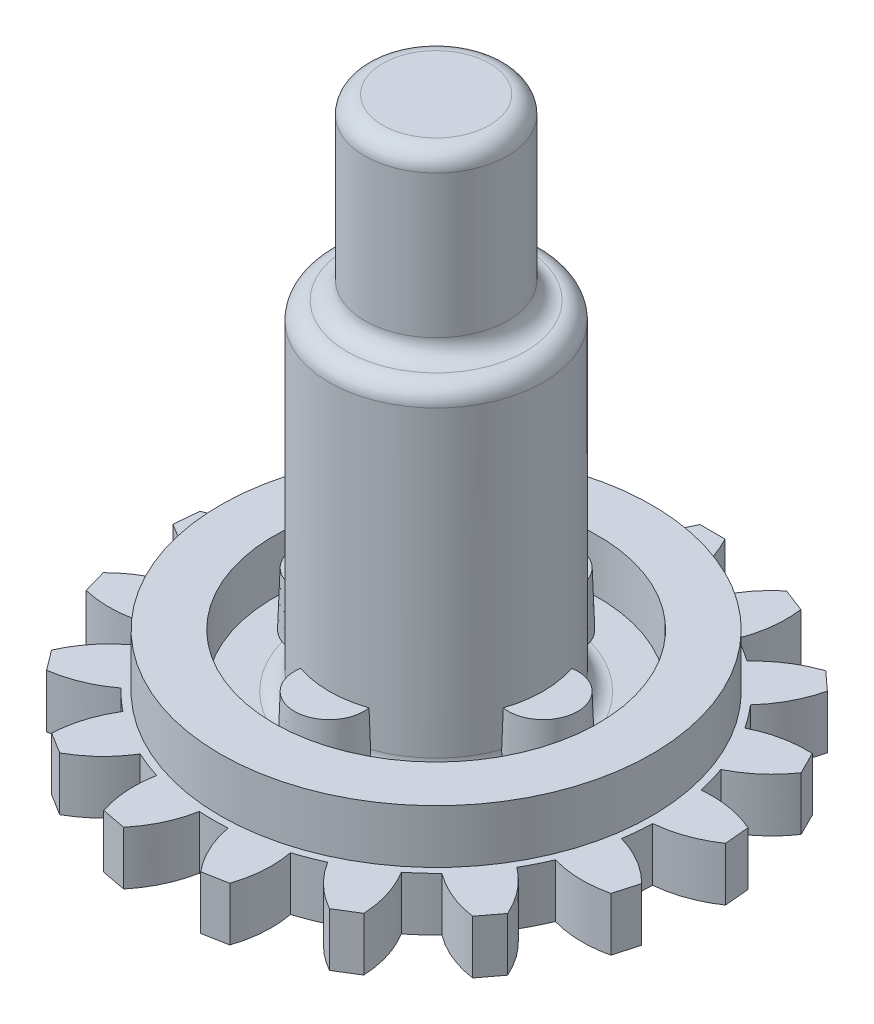
SolidWorks part; units mm, degrees
ref_plane "Front Plane" through (0, 0, 0) normal (0, 0, 1) x (1, 0, 0)
ref_plane "Top Plane" through (0, 0, 0) normal (0, 1, 0) x (1, 0, 0)
ref_plane "Right Plane" through (0, 0, 0) normal (1, 0, 0) x (0, 0, -1)
sketch "Sketch2" plane through (0, 0, 0) normal (0, 1, 0) x (1, 0, 0)
  line L0 (0, 12.5) -> (0, 15.5) construction
  line L1 (0, 14) -> (1.3, 14) construction
  line L2 (-0.7, 15.5) -> (0.7, 15.5)
  line L3 (4.9465, 14.7062) -> (6.252, 14.2005)
  line L4 (9.925, 11.9262) -> (10.9596, 10.9831)
  line L5 (13.563, 7.5356) -> (14.187, 6.2823)
  line L6 (15.3693, 2.1272) -> (15.4985, 0.7331)
  line L7 (15.0999, -3.5685) -> (14.7167, -4.9151)
  line L8 (12.7911, -8.7822) -> (11.9474, -9.8994)
  line L9 (8.7549, -12.8099) -> (7.5645, -13.5469)
  line L10 (3.5362, -15.1075) -> (2.16, -15.3647)
  line L11 (-2.16, -15.3647) -> (-3.5362, -15.1075)
  line L12 (-7.5645, -13.5469) -> (-8.7549, -12.8099)
  line L13 (-11.9474, -9.8994) -> (-12.7911, -8.7822)
  line L14 (-14.7167, -4.9151) -> (-15.0999, -3.5685)
  line L15 (-15.4985, 0.7331) -> (-15.3693, 2.1272)
  line L16 (-14.187, 6.2823) -> (-13.563, 7.5356)
  line L17 (-10.9596, 10.9831) -> (-9.925, 11.9262)
  line L18 (-6.252, 14.2005) -> (-4.9465, 14.7062)
  circle A0 centre (0, 0) radius 8.9
  circle A1 centre (0, 0) radius 12.5 construction
  arc A2 (1.5, 12.4097) -> (3.0842, 12.1135) centre (0, 0) cw
  arc A3 (5.8816, 11.0298) -> (7.2518, 10.1814) centre (0, 0) cw
  arc A4 (9.4689, 8.1603) -> (10.4401, 6.8742) centre (0, 0) cw
  arc A5 (11.7773, 4.1887) -> (12.2183, 2.6386) centre (0, 0) cw
  arc A6 (12.4951, -0.3486) -> (12.3464, -1.9533) centre (0, 0) cw
  arc A7 (11.5254, -4.8388) -> (10.8071, -6.2815) centre (0, 0) cw
  arc A8 (8.9992, -8.6755) -> (7.8082, -9.7613) centre (0, 0) cw
  arc A9 (5.2575, -11.3406) -> (3.7547, -11.9228) centre (0, 0) cw
  arc A10 (0.8058, -12.474) -> (-0.8058, -12.474) centre (0, 0) cw
  arc A11 (-3.7547, -11.9228) -> (-5.2575, -11.3406) centre (0, 0) cw
  arc A12 (-7.8082, -9.7613) -> (-8.9992, -8.6755) centre (0, 0) cw
  arc A13 (-10.8071, -6.2815) -> (-11.5254, -4.8388) centre (0, 0) cw
  arc A14 (-12.3464, -1.9533) -> (-12.4951, -0.3486) centre (0, 0) cw
  arc A15 (-12.2183, 2.6386) -> (-11.7773, 4.1887) centre (0, 0) cw
  arc A16 (-10.4401, 6.8742) -> (-9.4689, 8.1603) centre (0, 0) cw
  arc A17 (-7.2518, 10.1814) -> (-5.8816, 11.0298) centre (0, 0) cw
  arc A18 (-3.0842, 12.1135) -> (-1.5, 12.4097) centre (0, 0) cw
  spline S0 degree 2 poles (0.7, 15.5) (1.4969, 14.0574) (1.5, 12.4097) knots 0 0 0 1 1 1
  spline S1 degree 2 poles (-0.7, 15.5) (-1.4969, 14.0574) (-1.5, 12.4097) knots 0 0 0 1 1 1
  spline S2 degree 2 poles (6.252, 14.2005) (6.4739, 12.5674) (5.8816, 11.0298) knots 0 0 0 1 1 1
  spline S3 degree 2 poles (4.9465, 14.7062) (3.6823, 13.6488) (3.0842, 12.1135) knots 0 0 0 1 1 1
  spline S4 degree 2 poles (10.9596, 10.9831) (10.5766, 9.3801) (9.4689, 8.1603) knots 0 0 0 1 1 1
  spline S5 degree 2 poles (9.925, 11.9262) (8.3642, 11.3969) (7.2518, 10.1814) knots 0 0 0 1 1 1
  spline S6 degree 2 poles (14.187, 6.2823) (13.2508, 4.926) (11.7773, 4.1887) knots 0 0 0 1 1 1
  spline S7 degree 2 poles (13.563, 7.5356) (11.9164, 7.6058) (10.4401, 6.8742) knots 0 0 0 1 1 1
  spline S8 degree 2 poles (15.4985, 0.7331) (14.1355, -0.1934) (12.4951, -0.3486) knots 0 0 0 1 1 1
  spline S9 degree 2 poles (15.3693, 2.1272) (13.8593, 2.7875) (12.2183, 2.6386) knots 0 0 0 1 1 1
  spline S10 degree 2 poles (14.7167, -4.9151) (13.1111, -5.2867) (11.5254, -4.8388) knots 0 0 0 1 1 1
  spline S11 degree 2 poles (15.0999, -3.5685) (13.9304, -2.4073) (12.3464, -1.9533) knots 0 0 0 1 1 1
  spline S12 degree 2 poles (11.9474, -9.8994) (10.316, -9.666) (8.9992, -8.6755) knots 0 0 0 1 1 1
  spline S13 degree 2 poles (12.7911, -8.7822) (12.1201, -7.2769) (10.8071, -6.2815) knots 0 0 0 1 1 1
  spline S14 degree 2 poles (7.5645, -13.5469) (6.1276, -12.7398) (5.2575, -11.3406) knots 0 0 0 1 1 1
  spline S15 degree 2 poles (8.7549, -12.8099) (8.6729, -11.1638) (7.8082, -9.7613) knots 0 0 0 1 1 1
  spline S16 degree 2 poles (2.16, -15.3647) (1.1117, -14.093) (0.8058, -12.474) knots 0 0 0 1 1 1
  spline S17 degree 2 poles (3.5362, -15.1075) (4.0544, -13.543) (3.7547, -11.9228) knots 0 0 0 1 1 1
  spline S18 degree 2 poles (-3.5362, -15.1075) (-4.0544, -13.543) (-3.7547, -11.9228) knots 0 0 0 1 1 1
  spline S19 degree 2 poles (-2.16, -15.3647) (-1.1117, -14.093) (-0.8058, -12.474) knots 0 0 0 1 1 1
  spline S20 degree 2 poles (-8.7549, -12.8099) (-8.6729, -11.1638) (-7.8082, -9.7613) knots 0 0 0 1 1 1
  spline S21 degree 2 poles (-7.5645, -13.5469) (-6.1276, -12.7398) (-5.2575, -11.3406) knots 0 0 0 1 1 1
  spline S22 degree 2 poles (-12.7911, -8.7822) (-12.1201, -7.2769) (-10.8071, -6.2815) knots 0 0 0 1 1 1
  spline S23 degree 2 poles (-11.9474, -9.8994) (-10.316, -9.666) (-8.9992, -8.6755) knots 0 0 0 1 1 1
  spline S24 degree 2 poles (-15.0999, -3.5685) (-13.9304, -2.4073) (-12.3464, -1.9533) knots 0 0 0 1 1 1
  spline S25 degree 2 poles (-14.7167, -4.9151) (-13.1111, -5.2867) (-11.5254, -4.8388) knots 0 0 0 1 1 1
  spline S26 degree 2 poles (-15.3693, 2.1272) (-13.8593, 2.7875) (-12.2183, 2.6386) knots 0 0 0 1 1 1
  spline S27 degree 2 poles (-15.4985, 0.7331) (-14.1355, -0.1934) (-12.4951, -0.3486) knots 0 0 0 1 1 1
  spline S28 degree 2 poles (-13.563, 7.5356) (-11.9164, 7.6058) (-10.4401, 6.8742) knots 0 0 0 1 1 1
  spline S29 degree 2 poles (-14.187, 6.2823) (-13.2508, 4.926) (-11.7773, 4.1887) knots 0 0 0 1 1 1
  spline S30 degree 2 poles (-9.925, 11.9262) (-8.3642, 11.3969) (-7.2518, 10.1814) knots 0 0 0 1 1 1
  spline S31 degree 2 poles (-10.9596, 10.9831) (-10.5766, 9.3801) (-9.4689, 8.1603) knots 0 0 0 1 1 1
  spline S32 degree 2 poles (-4.9465, 14.7062) (-3.6823, 13.6488) (-3.0842, 12.1135) knots 0 0 0 1 1 1
  spline S33 degree 2 poles (-6.252, 14.2005) (-6.4739, 12.5674) (-5.8816, 11.0298) knots 0 0 0 1 1 1
  point P113 (0, 0)
  point P146 (0, 0)
  dimension "D1" = 17.8
  dimension "D5" = 25
  dimension "D2" = 0.7
  dimension "D3" = 1.5
  dimension "D4" = 1.3
  dimension "D6" = 3
  dimension "D7" = 17
  dimension "D8" = 17
extrude "Boss-Extrude1" add sketch "Sketch2" along normal mid plane 3
sketch "Sketch3" plane through (0, 1.5, 0) normal (0, 1, 0) x (1, 0, 0)
  circle A0 centre (0, 0) radius 9.1
  circle A1 centre (0, 0) radius 12.1
  dimension "D1" = 18.2
  dimension "D2" = 3
extrude "Boss-Extrude2" add sketch "Sketch3" along normal blind 3
sketch "Sketch4" plane through (0, -1.5, 0) normal (0, -1, 0) x (1, 0, 0)
  circle A0 centre (0, 0) radius 8.9 construction
  circle A1 centre (0, 0) radius 8.9
extrude "Boss-Extrude3" add sketch "Sketch4" against normal up to surface (3 mm away) up to face at (0, 1.5, 12.1)
sketch "Sketch5" plane through (0, 1.5, 0) normal (0, 1, 0) x (1, 0, 0)
  line L0 (6, 0) -> (-6, 0) construction
  line L1 (0, 0) -> (0, 9.1) construction
  circle A0 centre (-6, 0) radius 2.05
  circle A1 centre (0, 0) radius 9.1 construction
  circle A2 centre (6, 0) radius 2.05
  circle A3 centre (0, -6) radius 2.05
  circle A5 centre (0, 6) radius 2.05
  circle A6 centre (-6, 0) radius 2.05 [skipped]
  point P4 (0, 0)
  point P21 (0, 0)
  dimension "D1" = 4.1
  dimension "D2" = 12
  dimension "D3" = 4
extrude "Boss-Extrude4" add sketch "Sketch5" along normal blind 3 draft 2
sketch "Sketch6" plane through (0, 1.5, 0) normal (0, 1, 0) x (1, 0, 0)
  circle A0 centre (0, 0) radius 6
  dimension "D1" = 12
extrude "Boss-Extrude5" add sketch "Sketch6" along normal blind 19
sketch "Sketch7" plane through (0, 20.5, 0) normal (0, 1, 0) x (1, 0, 0)
  circle A0 centre (0, 0) radius 4
  dimension "D1" = 8
extrude "Boss-Extrude6" add sketch "Sketch7" along normal blind 10
fillet "Fillet1" radius 1 7 edges at (-4.2426, 1.5, -4.2426) (4.2426, 1.5, -4.2426) (4.2426, 1.5, 4.2426) (-4.2426, 1.5, 4.2426) (0, 30.5, 4) (0, 20.5, 6) (0, 20.5, 4)
